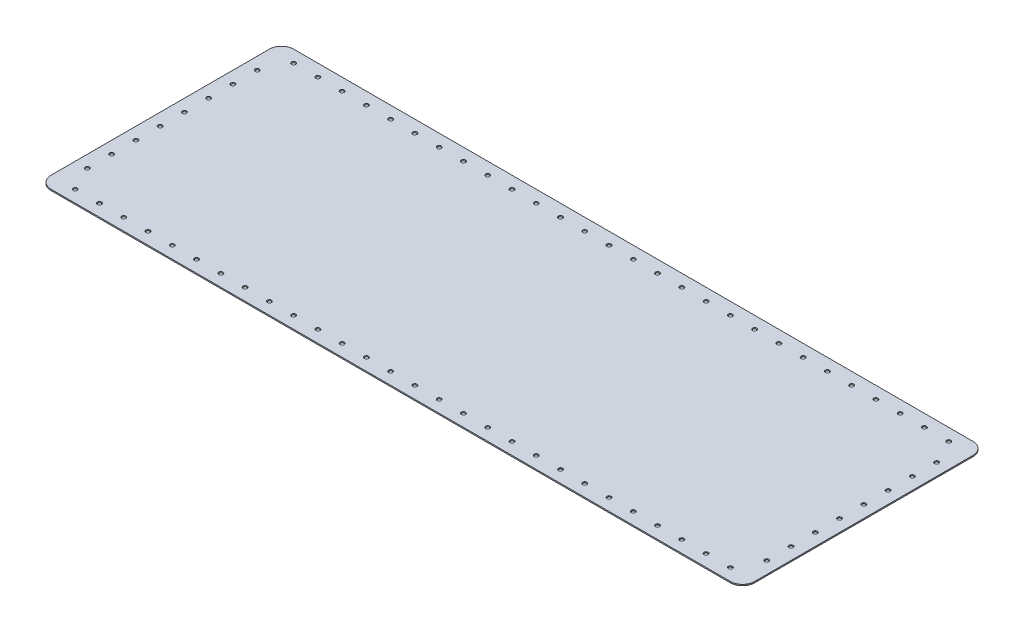
SolidWorks part; units mm, degrees
material "AISI 1020 Steel, Cold Rolled"
ref_plane "Front Plane" through (0, 0, 0) normal (0, 0, 1) x (1, 0, 0)
ref_plane "Top Plane" through (0, 0, 0) normal (0, 1, 0) x (1, 0, 0)
ref_plane "Right Plane" through (0, 0, 0) normal (1, 0, 0) x (0, 0, -1)
sketch "Sketch1" plane through (0, 0, 0) normal (0, 1, 0) x (1, 0, 0)
  line L1 (-290, 100) -> (290, 100)
  line L2 (-290, 100) -> (-290, -100)
  line L3 (-290, -100) -> (290, -100)
  line L4 (290, 100) -> (290, -100)
  line L5 (-290, 100) -> (290, -100) construction
  line L6 (-290, -100) -> (290, 100) construction
  point P0 (0, 0)
  dimension "D1" = 580
  dimension "D2" = 200
extrude "Boss-Extrude1" add sketch "Sketch1" along normal blind 1
fillet "Fillet1" radius 10 4 edges at (-290, 0.5, 100) (290, 0.5, 100) (290, 0.5, -100) (-290, 0.5, -100)
hole_wizard "M3 Clearance Hole1" positions "Sketch2" profile "Sketch3" hole size "M3" standard "ANSI Metric" end condition through all
sketch "Sketch2" plane through (0, 1, 0) normal (0, 1, 0) x (1, 0, 0)
  line L0 (280, 100) -> (-280, 100) construction
  line L1 (290, -90) -> (290, 90) construction
  line L2 (-0.55, 0) -> (0.55, 0) construction
  line L3 (0, -0.55) -> (0, 0.55) construction
  point P1 (280, 70)
  point P3 (270, 90)
  point P17 (250, 90)
  point P18 (230, 90)
  point P19 (210, 90)
  point P20 (190, 90)
  point P21 (170, 90)
  point P22 (150, 90)
  point P23 (130, 90)
  point P24 (110, 90)
  point P25 (90, 90)
  point P26 (70, 90)
  point P27 (50, 90)
  point P28 (30, 90)
  point P29 (10, 90)
  point P30 (-10, 90)
  point P31 (-30, 90)
  point P32 (-50, 90)
  point P33 (-70, 90)
  point P34 (-90, 90)
  point P35 (-110, 90)
  point P36 (-130, 90)
  point P37 (-150, 90)
  point P38 (-170, 90)
  point P39 (-190, 90)
  point P40 (-210, 90)
  point P41 (-230, 90)
  point P42 (-250, 90)
  point P43 (-270, 90)
  point P51 (280, 50.003)
  point P52 (280, 30.0061)
  point P53 (280, 10.0091)
  point P54 (280, -9.9878)
  point P55 (280, -29.9848)
  point P56 (280, -49.9817)
  point P57 (280, -69.9787)
  point P60 (270, -90)
  point P61 (250, -90)
  point P62 (230, -90)
  point P63 (210, -90)
  point P64 (190, -90)
  point P65 (170, -90)
  point P66 (150, -90)
  point P67 (130, -90)
  point P68 (110, -90)
  point P69 (90, -90)
  point P70 (70, -90)
  point P71 (50, -90)
  point P72 (30, -90)
  point P73 (10, -90)
  point P74 (-10, -90)
  point P75 (-30, -90)
  point P76 (-50, -90)
  point P77 (-70, -90)
  point P78 (-90, -90)
  point P79 (-110, -90)
  point P80 (-130, -90)
  point P81 (-150, -90)
  point P82 (-170, -90)
  point P83 (-190, -90)
  point P84 (-210, -90)
  point P85 (-230, -90)
  point P86 (-250, -90)
  point P87 (-270, -90)
  point P90 (-280, 70)
  point P91 (-280, 50.003)
  point P92 (-280, 30.0061)
  point P93 (-280, 10.0091)
  point P94 (-280, -9.9878)
  point P95 (-280, -29.9848)
  point P96 (-280, -49.9817)
  point P97 (-280, -69.9787)
  point P102 (0, 0)
  dimension "D1" = 30
  dimension "D2" = 10
  dimension "D3" = 20
  dimension "D4" = 10
  dimension "D6" = 20
  dimension "D8" = 19.997
  dimension "D5" = 28
  dimension "D7" = 8
sketch "Sketch3" plane through (280, 1, -70) normal (1, 0, 0) x (0, 0, 1)
  line L0 (0, 0) -> (0, 1)
  line L1 (0, 1) -> (1.7, 1)
  line L2 (1.7, 1) -> (1.7, 0.025)
  line L3 (1.7, 0.025) -> (1.725, 0)
  line L5 (1.725, 0) -> (0, 0)
  line L6 (-1.7, 0.025) -> (-1.725, 0) construction
  line L11 (0, -6.35) -> (0, 107.95) construction
  dimension "Thru Hole Dia." = 3.4
  dimension "Thru Hole Depth" = 1
  dimension "Near C'Sink Dia." = 3.45
  dimension "Near C'Sink Angle" = 90
